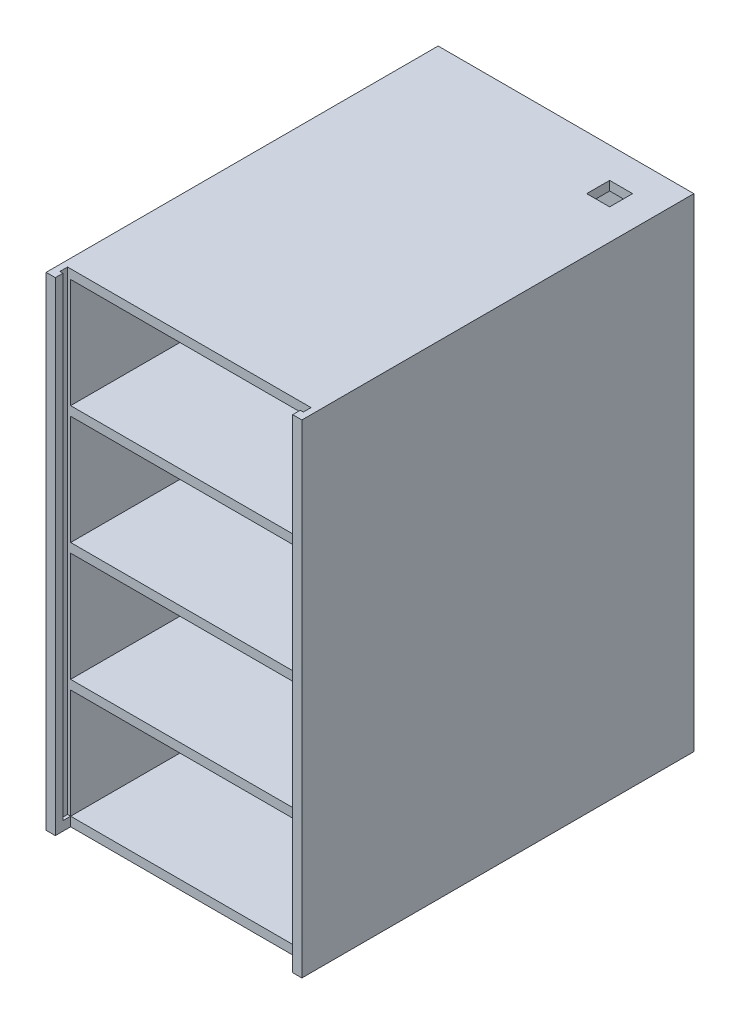
SolidWorks part; units mm, degrees
ref_plane "Front Plane" through (0, 0, 0) normal (0, 0, 1) x (1, 0, 0)
ref_plane "Top Plane" through (0, 0, 0) normal (0, 1, 0) x (1, 0, 0)
ref_plane "Right Plane" through (0, 0, 0) normal (1, 0, 0) x (0, 0, -1)
sketch "Sketch1" plane through (0, 0, 0) normal (0, 0, 1) x (1, 0, 0)
  line L0 (3, 119.1) -> (3, 116.1)
  line L1 (0, 0) -> (83.5, 0)
  line L2 (0, 0) -> (0, 157.8)
  line L3 (0, 157.8) -> (83.5, 157.8)
  line L4 (83.5, 0) -> (83.5, 157.8)
  line L5 (0, 157.8) -> (3, 157.8)
  line L6 (0, 157.8) -> (0, 154.8)
  line L7 (0, 154.8) -> (3, 154.8)
  line L8 (3, 157.8) -> (3, 154.8)
  line L9 (3, 154.8) -> (80.5, 154.8)
  line L10 (3, 154.8) -> (3, 119.1)
  line L11 (3, 119.1) -> (80.5, 119.1)
  line L12 (80.5, 154.8) -> (80.5, 119.1)
  line L13 (3, 80.4) -> (3, 77.4)
  line L14 (3, 116.1) -> (80.5, 116.1)
  line L15 (3, 116.1) -> (3, 80.4)
  line L16 (3, 80.4) -> (80.5, 80.4)
  line L17 (80.5, 116.1) -> (80.5, 80.4)
  line L18 (3, 41.7) -> (3, 38.7)
  line L19 (3, 77.4) -> (80.5, 77.4)
  line L20 (3, 77.4) -> (3, 41.7)
  line L21 (3, 41.7) -> (80.5, 41.7)
  line L22 (80.5, 77.4) -> (80.5, 41.7)
  line L24 (3, 38.7) -> (80.5, 38.7)
  line L25 (3, 38.7) -> (3, 3)
  line L26 (3, 3) -> (80.5, 3)
  line L27 (80.5, 38.7) -> (80.5, 3)
  dimension "D1" = 157.8
  dimension "D2" = 83.5
  dimension "D3" = 3
  dimension "D4" = 3
  dimension "D5" = 77.5
  dimension "D6" = 3
  dimension "D7" = 35.7
  dimension "D8" = 35.7
  dimension "D9" = 3
  dimension "D10" = 77.5
  dimension "D11" = 35.7
  dimension "D12" = 77.5
  dimension "D13" = 3
  dimension "D14" = 35.7
  dimension "D15" = 77.5
extrude "Boss-Extrude1" add sketch "Sketch1" along normal blind 123 contours L24 L27 L26 L25 L20 L15 L10 L7 L2 L1 L4 L3 L8 L9 L12 L11 L14 L17 L16 L19 L22 L21 | L8 L3 L2 L7 region at (41.9225, 78.5683, 0) region at (1.5, 156.3, 0)
extrude "Boss-Extrude2" add sketch "Sketch1<3>" along normal blind 3 contours L12 L9 L10 L11 | L17 L14 L15 L16 | L22 L19 L20 L21 | L27 L24 L25 L26 region at (41.75, 20.85, 0) region at (41.75, 59.55, 0) region at (41.75, 98.25, 0) region at (41.75, 136.95, 0)
sketch "Sketch1<3>" plane through (0, 0, 0) normal (0, 0, 1) x (1, 0, 0) same geometry as "Sketch1"
sketch "Sketch2" plane through (0, 119.1, 0) normal (0, 1, 0) x (1, 0, 0)
  line L0 (80.5, -123) -> (80.5, -3) construction
  line L1 (3, -3) -> (80.5, -3)
  line L2 (3, -3) -> (3, -30)
  line L3 (3, -30) -> (80.5, -30)
  line L4 (80.5, -3) -> (80.5, -30)
  dimension "D1" = 27
extrude "Cut-Extrude1" cut sketch "Sketch2" against normal blind 100
sketch "Sketch4" plane through (3, 0, 0) normal (1, 0, 0) x (0, 0, -1)
  line L0 (-33, 80.4) -> (-33, 90.4)
  line L1 (-30, 119.1) -> (-33, 119.1)
  line L2 (-30, 119.1) -> (-30, 129.1)
  line L3 (-30, 129.1) -> (-33, 129.1)
  line L4 (-33, 119.1) -> (-33, 129.1)
  line L5 (-30, 90.4) -> (-33, 90.4)
  line L6 (-30, 80.4) -> (-33, 80.4)
  line L7 (-30, 80.4) -> (-30, 90.4)
  line L8 (-33, 41.7) -> (-33, 51.7)
  line L9 (-30, 51.7) -> (-33, 51.7)
  line L10 (-30, 41.7) -> (-33, 41.7)
  line L11 (-30, 41.7) -> (-30, 51.7)
  line L12 (-33, 3) -> (-33, 13)
  line L13 (-30, 13) -> (-33, 13)
  line L14 (-30, 3) -> (-33, 3)
  line L15 (-30, 3) -> (-30, 13)
  dimension "D1" = 10
  dimension "D2" = 3
  dimension "D3" = 4
extrude "Boss-Extrude3" add sketch "Sketch4" along normal blind 10
sketch "Sketch5" plane through (80.5, 0, 0) normal (-1, 0, 0) x (0, 0, 1)
  line L0 (30, 90.4) -> (33, 90.4)
  line L1 (30, 119.1) -> (33, 119.1)
  line L2 (30, 119.1) -> (30, 129.1)
  line L3 (30, 129.1) -> (33, 129.1)
  line L4 (33, 119.1) -> (33, 129.1)
  line L5 (30, 80.4) -> (30, 90.4)
  line L6 (33, 80.4) -> (33, 90.4)
  line L7 (30, 80.4) -> (33, 80.4)
  line L8 (30, 51.7) -> (33, 51.7)
  line L9 (30, 41.7) -> (30, 51.7)
  line L10 (33, 41.7) -> (33, 51.7)
  line L11 (30, 41.7) -> (33, 41.7)
  line L12 (30, 13) -> (33, 13)
  line L13 (30, 3) -> (30, 13)
  line L14 (33, 3) -> (33, 13)
  line L15 (30, 3) -> (33, 3)
  dimension "D1" = 3
  dimension "D2" = 10
  dimension "D3" = 4
extrude "Boss-Extrude4" add sketch "Sketch5" along normal blind 10
sketch "Sketch7" plane through (0, 0, 123) normal (0, 0, 1) x (1, 0, 0)
  line L0 (0, 0) -> (83.5, 0) construction
  line L1 (0, 157.8) -> (3, 157.8)
  line L2 (0, 157.8) -> (0, 0)
  line L3 (0, 0) -> (3, 0)
  line L4 (3, 157.8) -> (3, 0)
  line L5 (83.5, 157.8) -> (83.5, 0)
  line L6 (80.5, 157.8) -> (83.5, 157.8)
  line L7 (80.5, 157.8) -> (80.5, 0)
  line L8 (80.5, 0) -> (83.5, 0)
  dimension "D1" = 3
  dimension "D2" = 2
extrude "Boss-Extrude5" add sketch "Sketch7" along normal blind 5
sketch "Sketch8" plane through (0, 157.8, 0) normal (0, 1, 0) x (1, 0, 0)
  line L1 (3, -123) -> (2, -123)
  line L2 (3, -123) -> (3, -125.5)
  line L3 (3, -125.5) -> (2, -125.5)
  line L4 (2, -123) -> (2, -125.5)
  line L5 (80.5, -123) -> (81.5, -123)
  line L6 (80.5, -123) -> (80.5, -125.5)
  line L7 (80.5, -125.5) -> (81.5, -125.5)
  line L8 (81.5, -123) -> (81.5, -125.5)
  dimension "D1" = 1
  dimension "D2" = 2.5
  dimension "D3" = 1
  dimension "D4" = 2.5
extrude "Cut-Extrude2" cut sketch "Sketch8" against normal blind 154.8
sketch "Sketch9" plane through (0, 157.8, 0) normal (0, 1, 0) x (1, 0, 0)
  line L1 (83.5, 0) -> (73.5, 0)
  line L2 (83.5, 0) -> (83.5, -10)
  line L3 (83.5, -10) -> (73.5, -10)
  line L4 (73.5, 0) -> (73.5, -10)
  line L5 (73.5, -10) -> (66, -10)
  line L6 (73.5, -10) -> (73.5, -17.5)
  line L7 (73.5, -17.5) -> (66, -17.5)
  line L8 (66, -10) -> (66, -17.5)
  dimension "D1" = 10
  dimension "D2" = 10
  dimension "D3" = 7.5
  dimension "D4" = 7.5
extrude "Cut-Extrude3" cut sketch "Sketch9" against normal blind 10 contours L5 L8 L7 L6 region at (69.75, 157.8, 13.75)
